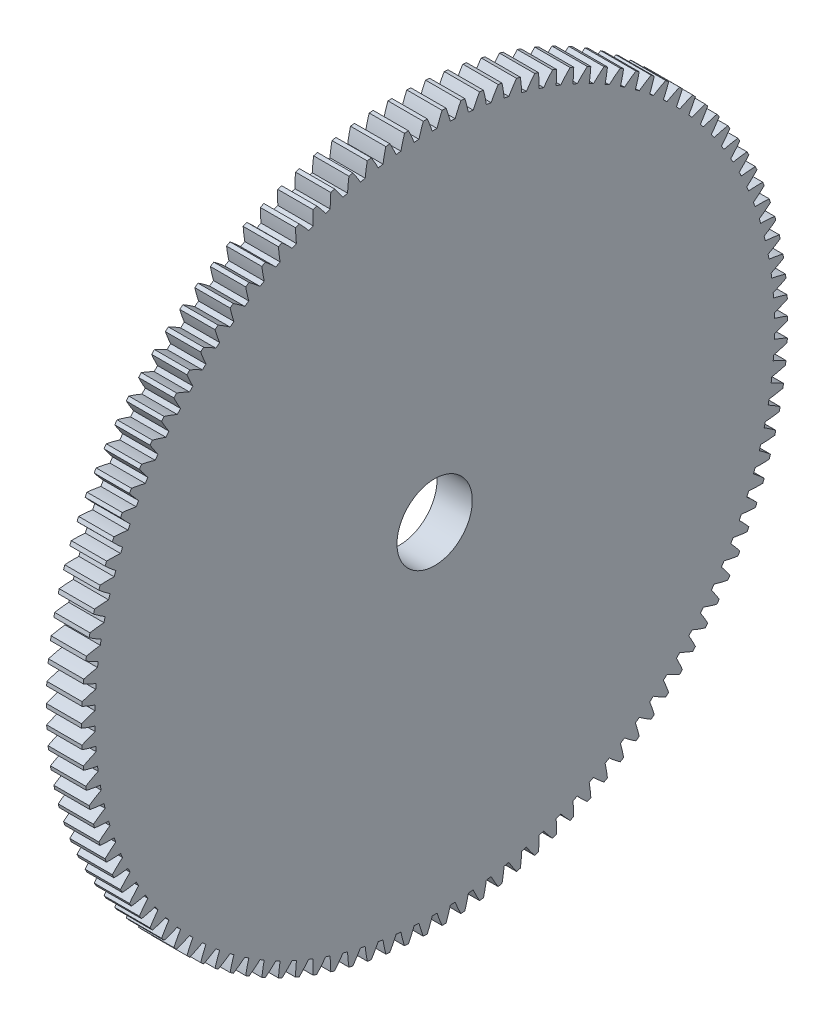
SolidWorks part; units mm, degrees
ref_plane "Plane1" through (0, 0, 0) normal (0, 0, 1) x (1, 0, 0)
ref_plane "Plane2" through (0, 0, 0) normal (0, 1, 0) x (1, 0, 0)
ref_plane "Plane3" through (0, 0, 0) normal (1, 0, 0) x (0, 0, -1)
sketch "HoldingSke" plane through (0, 0, 0) normal (0, 1, 0) x (1, 0, 0)
  line L0 (0, 0) -> (-0.4695, -0.8829)
  line L1 (-15, 0) -> (100, 0) construction
  line L2 (0, 0) -> (-2.1039, 2.3779)
  line L3 (0, 0) -> (-11.863, 4.5341)
  line L4 (0, 0) -> (-4.0544, 7.6251)
  line L5 (0, 0) -> (-46.8476, -17.4728)
  line L6 (0, 0) -> (-4.9738, -3.3558)
  line L7 (-2.1039, 2.3779) -> (8.6586, 51.2059)
  line L8 (-76.2, 54.61) -> (-76.1, 54.61)
  line L9 (-71.009, 38.7566) -> (-53.1078, 45.2721)
  line L10 (-76.2, 71.12) -> (104.1128, 71.12)
  line L11 (0, 0) -> (-6, 0)
  line L12 (-76.2, 101.6) -> (-76.162, 101.6)
  line L13 (24.9733, 27.94) -> (52.9518, 28.4284)
  line L14 (24.9733, 27.94) -> (24.9743, 27.94)
  line L15 (24.9733, 27.94) -> (100.4006, 29.5858)
  line L16 (-63.627, -1) -> (-12.827, -1)
  circle A0 centre (0, 0) radius 0.5
  circle A1 centre (0, 0) radius 37.5
  circle A2 centre (0, 0) radius 37.5
  circle A3 centre (0, 0) radius 0.5
  dimension "MHD" = 75
  dimension "Hub_dia" = 75
  dimension "Bore" = 1
  dimension "MBD" = 1
  dimension "Num_teeth" = 118
  dimension "Pitch" = 1
  dimension "Overall_len" = 50
  dimension "Show_teeth" = 118
  dimension "Thickness" = 6
  dimension "OAL" = 50.0001
  dimension "T_dim" = 0.1
  dimension "Ap" = 20
  dimension "H" = 19.05
  dimension "Pitch_radius" = 180.3128
  dimension "Width" = 6
  dimension "Backlash" = 0.038
  dimension "Addendum_fac" = 1
  dimension "Dedendum_fac" = 1.25
  dimension "Clearance_fac" = 0.25
  dimension "Dedendum_add" = 0.001
  dimension "Module" = 1
sketch "BasProSke" plane through (0, 0, 0) normal (0, 1, 0) x (1, 0, 0)
  line L0 (-10, 0) -> (60, 0) construction
  line L1 (0, 0) -> (0, 60)
  line L2 (0, 0) -> (6, 0)
  line L3 (6, 0) -> (6, 60)
  line L4 (6, 60) -> (0, 60)
  dimension "Thickness" = 6
  dimension "Diameter" = 120
revolve "Base-Revolve" add sketch "BasProSke" angle 360 about L0
sketch "TooCutSke" plane through (0, 0, 0) normal (1, 0, 0) x (0, 0, -1)
  line L1 (0, 0) -> (0, 107) construction
  line L2 (0, 0) -> (-0.8519, 58.9938) construction
  line L3 (0, 0) -> (-3.141, 117.9494) construction
  line L4 (-0.8519, 58.9938) -> (-1.5705, 58.9747) construction
  arc A0 (0.4111, 57.7475) -> (-0.4111, 57.7475) centre (0, 0) ccw
  arc A1 (1.2719, 60.0119) -> (-1.2719, 60.0119) centre (0, 0) ccw
  circle A2 centre (0, 0) radius 59 construction
  circle A3 centre (0, 0) radius 55.4419 construction
  arc A4 (-0.4111, 57.7475) -> (-1.2719, 60.0119) centre (-22.872, 50.5042) ccw
  arc A5 (1.2719, 60.0119) -> (0.4111, 57.7475) centre (22.872, 50.5042) ccw
  dimension "Root_dia" = 115.498
  dimension "Overcut_dia" = 120.0508
  dimension "Pitch_dia" = 118
  dimension "Base_dia" = 110.8837
  dimension "Flank_rad" = 23.6
  dimension "Half_ang" = 1.525
  dimension "Half_CT" = 0.7189
extrude "ToothCut" cut sketch "TooCutSke" along normal through all
fillet "Breaks" [suppressed] radius 0.02 tangent propagation no
fillet "RootFillets" [suppressed] radius 0.251
pattern_circular "TeethCuts" count 118 every 3.051 about axis through (-10, 0, 0) along (1, 0, 0) of "ToothCut", "RootFillets", "Breaks"
sketch "HubNeaOneSke" plane through (0, 0, 0) normal (-1, 0, 0) x (0, 0, 1)
  circle A0 centre (0, 0) radius 37.5
  dimension "Diameter" = 75
extrude "HubNearOne" [suppressed] add sketch "HubNeaOneSke" along normal blind 44.0001
sketch "HubNeaBotSke" plane through (0, 0, 0) normal (-1, 0, 0) x (0, 0, 1)
  circle A0 centre (0, 0) radius 37.5
  dimension "Diameter" = 75
extrude "HubNearBoth" [suppressed] add sketch "HubNeaBotSke" along normal blind 22
ref_plane "FarPln" through (6, 0, 0) normal (1, 0, 0) x (0, 0, -1)
sketch "HubFarSke" plane through (6, 0, 0) normal (1, 0, 0) x (0, 0, -1)
  circle A0 centre (0, 0) radius 37.5
  dimension "Diameter" = 75
extrude "HubFar" [suppressed] add sketch "HubFarSke" along normal blind 22
sketch "BorSke" plane through (0, 0, 0) normal (1, 0, 0) x (0, 0, -1)
  circle A0 centre (0, 0) radius 6.4
  dimension "Diameter" = 12.8
extrude "Bore" cut sketch "BorSke" along normal mid plane 100.0001
sketch "KeySke" plane through (0, 0, 0) normal (1, 0, 0) x (0, 0, -1)
  line L0 (-0.05, 0) -> (-0.05, 0.6)
  line L1 (-0.05, 0.6) -> (0.05, 0.6)
  line L2 (0.05, 0.6) -> (0.05, 0)
  line L3 (0, 0) -> (0, 34) construction
  line L4 (-0.05, 0) -> (0.05, 0)
  dimension "Offset" = 0.6
  dimension "Width" = 0.1
extrude "Keyway" [suppressed] cut sketch "KeySke" along normal mid plane 100.0001
pattern_circular "Keyway2" [suppressed] count 2 every 90 about axis through (-10, 0, 0) along (1, 0, 0) reverse direction yes
equation "' \"Module@HoldingSke\" = 6.35"
equation "' \"Num_teeth@HoldingSke\" = 12"
equation "' \"Ap@HoldingSke\" =  20"
equation "' \"Ap@HoldingSke\" = 20"
equation "' \"Width@HoldingSke\" = 0.5 * 25.4"
equation "' \"Hub_dia@HoldingSke\"= 1 * 25.4"
equation "' \"Hub_dia@HoldingSke\" = 1 * 25.4"
equation "' \"Overall_len@HoldingSke\" = 1.0 * 25.4"
equation "' \"Bore@HoldingSke\" = 0.75 * 25.4"
equation "' \"T_dim@HoldingSke\" = 0.1 * 25.4"
equation "' \"Width@KeySke\" = 0.25 * 25.4"
equation "' \"Show_teeth@HoldingSke\" = 13"
equation "' \"Backlash@HoldingSke\" = 0.009 * 25.4"
equation "' \"Addendum_fac@HoldingSke\" = 1.0"
equation "' \"Dedendum_fac@HoldingSke\" = 1.25"
equation "' \"Dedendum_add@HoldingSke\" = 0.00005 * 25.4"
equation "' \"Clearance_fac@HoldingSke\" = 0.25"
equation "\"Pitch@HoldingSke\" = 1 / \"Module@HoldingSke\""
equation "\"Overcut_dia@TooCutSke\" = (\"Num_teeth@HoldingSke\" + 2 * \"Addendum_fac@HoldingSke\") / \"Pitch@HoldingSke\" + 0.002 * 25.4"
equation "\"Pitch_dia@TooCutSke\" = \"Num_teeth@HoldingSke\" / \"Pitch@HoldingSke\""
equation "\"Base_dia@TooCutSke\" = \"Num_teeth@HoldingSke\" / \"Pitch@HoldingSke\" * cos((\"Ap@HoldingSke\"  * 3.14159265 / 180))"
equation "\"Root_dia@TooCutSke\" = (\"Num_teeth@HoldingSke\" + 2) / \"Pitch@HoldingSke\" - 2 * (\"Addendum_fac@HoldingSke\" + \"Dedendum_fac@HoldingSke\") / \"Pitch@HoldingSke\" - \"Dedendum_add@HoldingSke\" * 2"
equation "\"Half_ang@TooCutSke\" = 180 / \"Num_teeth@HoldingSke\""
equation "\"Half_CT@TooCutSke\" = \"Num_teeth@HoldingSke\" / \"Pitch@HoldingSke\" * sin((3.14159265 / 2 / \"Num_teeth@HoldingSke\")) / 2 - 7 * \"Backlash@HoldingSke\" / 4"
equation "\"Flank_rad@TooCutSke\" = \"Num_teeth@HoldingSke\" / \"Pitch@HoldingSke\" / 5"
equation "\"Radius@RootFillets\" = \"Clearance_fac@HoldingSke\" / \"Pitch@HoldingSke\" + \"Dedendum_add@HoldingSke\""
equation "\"Break_rad@Breaks\" = 0.02 / \"Pitch@HoldingSke\""
equation "\"Thickness@HoldingSke\" = \"Width@HoldingSke\""
equation "\"OAL@HoldingSke\" = \"Thickness@HoldingSke\""
equation "\"MHD@HoldingSke\" = (\"Num_teeth@HoldingSke\" + 2) / \"Pitch@HoldingSke\" - 2 * (\"Addendum_fac@HoldingSke\" + \"Dedendum_fac@HoldingSke\")  / \"Pitch@HoldingSke\" - \"Dedendum_add@HoldingSke\" * 2"
equation "\"MBD@HoldingSke\" = (\"Num_teeth@HoldingSke\" + 2) / \"Pitch@HoldingSke\" - 2 * (\"Addendum_fac@HoldingSke\" + \"Dedendum_fac@HoldingSke\")  / \"Pitch@HoldingSke\" - \"Dedendum_add@HoldingSke\" * 2 - 0.002 * 25.4"
equation "\"MHD@HoldingSke\" = ((sgn( \"MHD@HoldingSke\" - \"Hub_dia@HoldingSke\" )-1)*( \"MHD@HoldingSke\" - \"Hub_dia@HoldingSke\" ))/-2+ \"Hub_dia@HoldingSke\""
equation "\"MBD@HoldingSke\" = ((sgn( \"MBD@HoldingSke\" - \"Bore@HoldingSke\" )-1)*( \"MBD@HoldingSke\" - \"Bore@HoldingSke\" ))/-2+ \"Bore@HoldingSke\""
equation "\"OAL@HoldingSke\" = ((sgn( \"OAL@HoldingSke\" - \"Overall_len@HoldingSke\" )+1)*( \"OAL@HoldingSke\" - \"Overall_len@HoldingSke\" ))/2 + \"Overall_len@HoldingSke\" + 0.000002 * 25.4"
equation "\"Num_teeth@TeethCuts\" = int( \"Show_teeth@HoldingSke\" ) + 1"
equation "\"Num_teeth@TeethCuts\" = ((sgn( \"Num_teeth@TeethCuts\" - \"Num_teeth@HoldingSke\" )-1)*( \"Num_teeth@TeethCuts\" - \"Num_teeth@HoldingSke\" ))/-2+ \"Num_teeth@HoldingSke\""
equation "\"Num_teeth@TeethCuts\" = ((sgn( \"Num_teeth@TeethCuts\" - 2.0)+1)*( \"Num_teeth@TeethCuts\" - 2.0))/2 +2.0"
equation "\"Angle@TeethCuts\" = 360.0 / \"Num_teeth@HoldingSke\""
equation "\"Diameter@BasProSke\" = (\"Num_teeth@HoldingSke\" + 2 * \"Addendum_fac@HoldingSke\") / \"Pitch@HoldingSke\""
equation "\"Thickness@BasProSke\"  = \"Thickness@HoldingSke\""
equation "' \"Fillet_rad@BasProSke\" =  \"Thickness@HoldingSke\" * 0.05"
equation "' \"Fillet_rad@BasProSke\" = \"Thickness@HoldingSke\" * 0.05"
equation "\"MHD@HoldingSke\" = ((sgn( \"MHD@HoldingSke\" - \"Root_dia@TooCutSke\" )-1)*( \"MHD@HoldingSke\" - \"Root_dia@TooCutSke\" ))/-2+ \"Root_dia@TooCutSke\""
equation "\"Diameter@HubNeaOneSke\" = \"MHD@HoldingSke\""
equation "\"Length@HubNearOne\" = \"OAL@HoldingSke\" - \"Thickness@BasProSke\""
equation "\"Diameter@HubNeaBotSke\" = \"MHD@HoldingSke\""
equation "\"Length@HubNearBoth\" = ( \"OAL@HoldingSke\" - \"Thickness@BasProSke\" ) / 2.0"
equation "\"Thickness@FarPln\" = \"Thickness@BasProSke\""
equation "\"Diameter@HubFarSke\" = \"MHD@HoldingSke\""
equation "\"Length@HubFar\" = ( \"OAL@HoldingSke\" - \"Thickness@BasProSke\" ) / 2.0"
equation "\"D1@Bore\" = \"OAL@HoldingSke\" * 2.0"
equation "\"D1@Keyway\" = \"OAL@HoldingSke\" * 2.0"
equation "\"Offset@KeySke\" = \"T_dim@HoldingSke\" + \"MBD@HoldingSke\" / 2.0"
